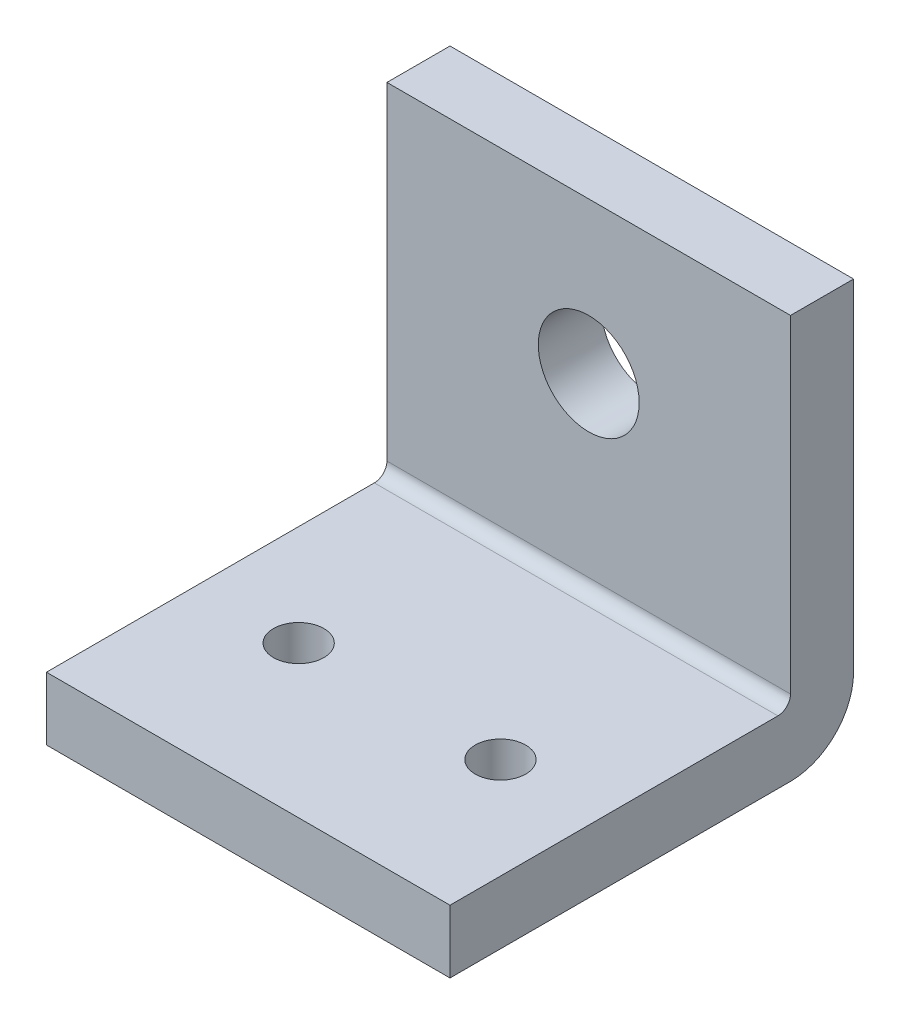
SolidWorks part; units mm, degrees
ref_plane "Front Plane" through (0, 0, 0) normal (0, 0, 1) x (1, 0, 0)
ref_plane "Top Plane" through (0, 0, 0) normal (0, 1, 0) x (1, 0, 0)
ref_plane "Right Plane" through (0, 0, 0) normal (1, 0, 0) x (0, 0, -1)
sketch "Sketch1" plane through (0, 0, 0) normal (0, 1, 0) x (1, 0, 0)
  line L0 (20, 0) -> (20, -37.8705) construction
  line L1 (0, 0) -> (40, 0)
  line L2 (0, 0) -> (0, 40)
  line L3 (0, 40) -> (40, 40)
  line L4 (40, 0) -> (40, 40)
  line L5 (0, 33.75) -> (40, 33.75)
  line L6 (10, 15) -> (30, 15) construction
  circle A0 centre (30, 15) radius 2.5
  circle A1 centre (10, 15) radius 2.5
  point P13 (20, 15)
  point P14 (40, 34.0136)
  point P15 (20, 40)
  point P16 (0, 33.9349)
  dimension "D2" = 5
  dimension "D1" = 40
  dimension "D3" = 20
  dimension "D4" = 15
  dimension "D5" = 6.25
extrude "Boss-Extrude1" add sketch "Sketch1" along normal blind 6.25 contours L5 L2 L1 L4 A1 A0 region at (20, 0, -16.9312)
extrude "Boss-Extrude2" add sketch "Sketch1<3>" along normal blind 40 contours L2 L5 L4 L3 region at (20, 0, -36.875)
sketch "Sketch1<3>" plane through (0, 0, 0) normal (0, 1, 0) x (1, 0, 0) same geometry as "Sketch1"
fillet "Fillet1" radius 6.25 1 edges at (20, 0, -40)
fillet "Fillet2" radius 1.25 1 edges at (20, 6.25, -33.75)
sketch "Sketch2" plane through (0, 0, -33.75) normal (0, 0, 1) x (1, 0, 0)
  line L0 (0, 40) -> (40, 40) construction
  circle A0 centre (20, 25) radius 5
  point P2 (0, 0)
  point P5 (20, 40)
  dimension "D1" = 10
  dimension "D2" = 15
extrude "Cut-Extrude1" cut sketch "Sketch2" against normal blind 40
